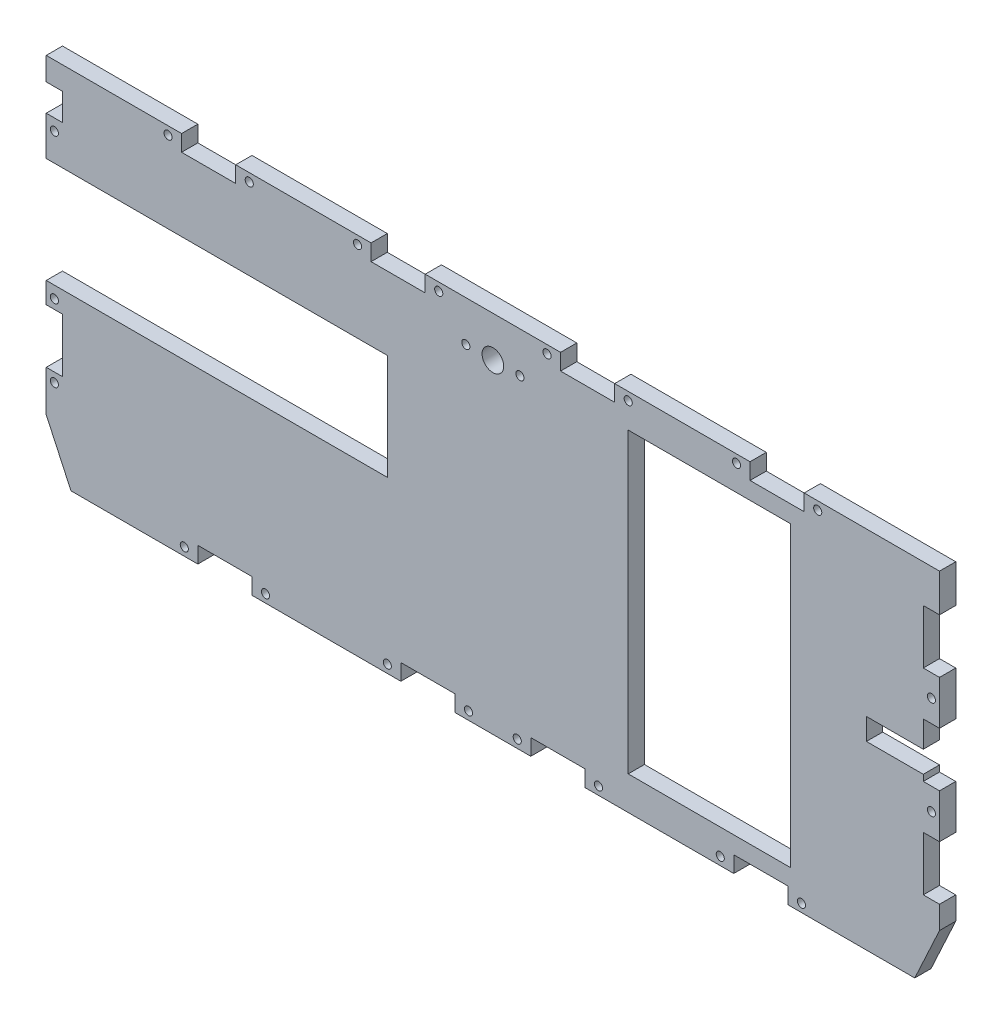
SolidWorks part; units mm, degrees
ref_plane "Plan de face" through (0, 0, 0) normal (0, 0, 1) x (1, 0, 0)
ref_plane "Plan de dessus" through (0, 0, 0) normal (0, 1, 0) x (1, 0, 0)
ref_plane "Plan de droite" through (0, 0, 0) normal (1, 0, 0) x (0, 0, -1)
sketch "Esquisse1" plane through (0, 0, 0) normal (0, 0, 1) x (1, 0, 0)
  line L0 (0, 124.9429) -> (0, -204.46) construction
  line L1 (-165, 96.73) -> (165, 96.73)
  line L2 (165, 96.73) -> (165, -18.27)
  line L3 (165, -18.27) -> (123, -109.0224)
  line L4 (123, -109.0224) -> (-123, -109.0224)
  line L5 (-211.9802, 0) -> (248.5953, 0) construction
  line L6 (-123, -109.0224) -> (-165, -18.27)
  line L7 (-165, -18.27) -> (-165, 96.73)
  dimension "D2" = 165
  dimension "D3" = 330
  dimension "D4" = 100
  dimension "D5" = 115
  dimension "D6" = 100
  dimension "D7" = 246
  dimension "D8" = 205.7524
  dimension "D9" = 96.73
  dimension "D10" = 115
extrude "Boss.-Extru.1" add sketch "Esquisse1" along normal blind 6
sketch "Esquisse3" plane through (0, 0, 0) normal (0, 0, -1) x (-1, 0, 0)
  line L0 (165, 96.73) -> (165, -18.27) construction
  line L1 (165, -3.06) -> (159, -3.06)
  line L2 (165, -3.06) -> (165, 16.94)
  line L3 (165, 16.94) -> (159, 16.94)
  line L4 (159, -3.06) -> (159, 16.94)
  line L5 (123, -109.0224) -> (-123, -109.0224) construction
  line L6 (165, 78.2326) -> (159, 78.2326)
  line L7 (165, 78.2326) -> (165, 88.2326)
  line L8 (165, 88.2326) -> (159, 88.2326)
  line L9 (159, 78.2326) -> (159, 88.2326)
  line L10 (-14, -38.02) -> (-14, -32.02)
  line L11 (109, -38.02) -> (89, -38.02)
  line L12 (109, -38.02) -> (109, -32.02)
  line L13 (109, -32.02) -> (89, -32.02)
  line L15 (0, -209.4812) -> (0, 177.1799) construction
  line L16 (-110, 84.355) -> (-50, 84.355)
  line L17 (-165, 82.73) -> (-159, 82.73)
  line L18 (89, -38.02) -> (89, -32.02)
  line L19 (34, -38.02) -> (14, -38.02)
  line L20 (34, -38.02) -> (34, -32.02)
  line L21 (34, -32.02) -> (14, -32.02)
  line L22 (-165, 82.73) -> (-165, 62.73)
  line L23 (-165, 62.73) -> (-159, 62.73)
  line L24 (-159, 82.73) -> (-159, 62.73)
  line L25 (-165, 46.44) -> (-159, 46.44)
  line L26 (-165, 46.44) -> (-165, 26.44)
  line L27 (-165, 26.44) -> (-159, 26.44)
  line L28 (-159, 46.44) -> (-159, 26.44)
  line L29 (-165, 10.15) -> (-159, 10.15)
  line L30 (-165, 96.73) -> (165, 96.73) construction
  line L31 (115, 96.73) -> (95, 96.73)
  line L32 (115, 96.73) -> (115, 90.73)
  line L33 (115, 90.73) -> (95, 90.73)
  line L34 (95, 96.73) -> (95, 90.73)
  line L35 (-25, 96.73) -> (-25, 90.73)
  line L36 (45, 96.73) -> (25, 96.73)
  line L37 (45, 96.73) -> (45, 90.73)
  line L38 (45, 90.73) -> (25, 90.73)
  line L39 (25, 96.73) -> (25, 90.73)
  line L40 (-45, 90.73) -> (-25, 90.73)
  line L41 (-45, 96.73) -> (-45, 90.73)
  line L42 (-45, 96.73) -> (-25, 96.73)
  line L43 (-95, 96.73) -> (-95, 90.73)
  line L44 (-115, 90.73) -> (-95, 90.73)
  line L45 (-115, 96.73) -> (-115, 90.73)
  line L46 (-115, 96.73) -> (-95, 96.73)
  line L47 (-165, 10.15) -> (-165, -9.85)
  line L48 (14, -38.02) -> (14, -32.02)
  line L49 (-34, -32.02) -> (-14, -32.02)
  line L50 (-34, -38.02) -> (-34, -32.02)
  line L51 (-34, -38.02) -> (-14, -38.02)
  line L52 (-165, -9.85) -> (-159, -9.85)
  line L53 (165, 63.73) -> (39, 63.73)
  line L54 (165, 63.73) -> (165, 24.73)
  line L55 (165, 24.73) -> (39, 24.73)
  line L56 (-159, 10.15) -> (-159, -9.85)
  line L57 (-89, -38.02) -> (-89, -32.02)
  line L58 (-109, -32.02) -> (-89, -32.02)
  line L59 (-109, -38.02) -> (-109, -32.02)
  line L60 (-109, -38.02) -> (-89, -38.02)
  line L62 (-110, 84.355) -> (-110, -25.645)
  line L63 (-110, -25.645) -> (-50, -25.645)
  line L64 (-50, 84.355) -> (-50, -25.645)
  line L65 (-165, -18.27) -> (-165, 96.73) construction
  line L66 (39, 63.73) -> (39, 24.73)
  dimension "D1" = 20
  dimension "D2" = 6
  dimension "D3" = 6
  dimension "D4" = 10
  dimension "D5" = 6
  dimension "D6" = 20
  dimension "D7" = 60
  dimension "D8" = 55
  dimension "D9" = 8.4974
  dimension "D10" = 20
  dimension "D11" = 20
  dimension "D12" = 50
  dimension "D13" = 50
  dimension "D14" = 6
  dimension "D15" = 110
  dimension "D16" = 56
  dimension "D17" = 55
  dimension "D18" = 20
  dimension "D19" = 20
  dimension "D20" = 20
  dimension "D21" = 6
  dimension "D22" = 6
  dimension "D23" = 20
  dimension "D24" = 71.0024
  dimension "D25" = 71.0024
  dimension "D26" = 33
  dimension "D27" = 39
  dimension "D28" = 126
  dimension "D29" = 6.375
  dimension "D30" = 15.21
  dimension "D31" = 6
  dimension "D32" = 6
  dimension "D33" = 6
  dimension "D34" = 14
  dimension "D35" = 16.29
  dimension "D36" = 16.29
extrude "Enlèv. mat.-Extru.2" cut sketch "Esquisse3" against normal blind 6
sketch "Esquisse4" plane through (0, 0, 0) normal (0, 0, -1) x (-1, 0, 0)
  line L0 (159, 78.2326) -> (165, 78.2326) construction
  line L1 (115, 90.73) -> (115, 96.73) construction
  line L2 (120.102, -35.02) -> (4.7601, -35.02) construction
  line L3 (14, -32.02) -> (14, -38.02) construction
  line L4 (34, -38.02) -> (34, -32.02) construction
  line L5 (89, -32.02) -> (89, -38.02) construction
  line L6 (26.5287, 81.73) -> (-31.7243, 81.73) construction
  line L7 (109, -38.02) -> (109, -32.02) construction
  line L8 (165, 78.2326) -> (165, 63.73) construction
  line L9 (-120.102, -35.02) -> (-4.7601, -35.02) construction
  line L10 (-25, 96.73) -> (25, 96.73) construction
  line L11 (143.8632, 93.73) -> (-5, 93.73) construction
  line L12 (45, 96.73) -> (95, 96.73) construction
  line L13 (-162, -27.3544) -> (-162, 100.425) construction
  line L14 (95, 96.73) -> (95, 90.73) construction
  line L15 (45, 90.73) -> (45, 96.73) construction
  line L16 (25, 96.73) -> (25, 90.73) construction
  line L17 (0, 142.2997) -> (0, -202.2086) construction
  line L18 (-165, -18.27) -> (-165, -9.85) construction
  line L19 (-80, 84.355) -> (-80, -25.645) construction
  line L21 (165, 16.94) -> (159, 16.94) construction
  line L22 (162, -8.8216) -> (162, 103.5789) construction
  line L25 (-50, 84.355) -> (-110, 84.355) construction
  line L26 (-110, -25.645) -> (-50, -25.645) construction
  line L27 (-159, 46.44) -> (-165, 46.44) construction
  line L28 (-165, 26.44) -> (-159, 26.44) construction
  line L31 (159, -3.06) -> (165, -3.06) construction
  circle A0 centre (162, 20.335) radius 1.5
  circle A1 centre (114, -35.02) radius 1.5
  circle A2 centre (162, 73.9826) radius 1.5
  circle A3 centre (84, -35.02) radius 1.5
  circle A4 centre (39, -35.02) radius 1.5
  circle A5 centre (162, -6.46) radius 1.5
  circle A6 centre (9, -35.02) radius 1.5
  circle A7 centre (-9, -35.02) radius 1.5
  circle A8 centre (-39, -35.02) radius 1.5
  circle A9 centre (-84, -35.02) radius 1.5
  circle A10 centre (120, 93.73) radius 1.5
  circle A11 centre (-114, -35.02) radius 1.5
  circle A12 centre (90, 93.73) radius 1.5
  circle A13 centre (0, 81.73) radius 4
  circle A14 centre (50, 93.73) radius 1.5
  circle A15 centre (20, 93.73) radius 1.5
  circle A16 centre (-162, 18.29) radius 1.5
  circle A17 centre (-162, 54.585) radius 1.5
  circle A18 centre (-20, 93.73) radius 1.5
  circle A19 centre (-50, 93.73) radius 1.5
  circle A20 centre (-90, 93.73) radius 1.5
  circle A21 centre (-120, 93.73) radius 1.5
  circle A22 centre (-10, 81.73) radius 1.5
  circle A23 centre (10, 81.73) radius 1.5
  dimension "D3" = 3
  dimension "D10" = 3
  dimension "D11" = 3
  dimension "D12" = 3
  dimension "D13" = 5
  dimension "D14" = 5
  dimension "D18" = 3
  dimension "D19" = 3
  dimension "D29" = 3
  dimension "D30" = 8.15
  dimension "D31" = 3
  dimension "D32" = 10
  dimension "D33" = 3
  dimension "D34" = 3
  dimension "D35" = 10
  dimension "D40" = 5
  dimension "D5" = 3.395
  dimension "D8" = 5
  dimension "D15" = 5
  dimension "D16" = 5
  dimension "D20" = 3.4
  dimension "D17" = 3
  dimension "D21" = 3
  dimension "D22" = 3
  dimension "D23" = 3
  dimension "D25" = 8
  dimension "D27" = 8.145
  dimension "D9" = 3
  dimension "D7" = 3
  dimension "D24" = 3
  dimension "D6" = 4.25
  dimension "D26" = 3
  dimension "D28" = 3
  dimension "D36" = 15
  dimension "D38" = 5
  dimension "D42" = 5
extrude "Enlèv. mat.-Extru.3" cut sketch "Esquisse4" against normal blind 6
sketch "Esquisse5" plane through (0, 0, 0) normal (0, 0, -1) x (-1, 0, 0)
  line L0 (45, 96.73) -> (95, 96.73) construction
  line L1 (209.7155, -38.02) -> (-246.3297, -38.02)
  line L2 (209.7155, -38.02) -> (209.7155, -174.249)
  line L3 (209.7155, -174.249) -> (-246.3297, -174.249)
  line L4 (-246.3297, -38.02) -> (-246.3297, -174.249)
  dimension "D1" = 134.75
extrude "Enlèv. mat.-Extru.4" cut sketch "Esquisse5" against normal blind 6
sketch "Esquisse6" plane through (0, 0, 0) normal (0, 0, -1) x (-1, 0, 0)
  line L0 (-159, 26.44) -> (-159, 46.44) construction
  line L1 (-159, 36.73) -> (-138, 36.73)
  line L2 (-159, 36.73) -> (-159, 28.73)
  line L3 (-159, 28.73) -> (-138, 28.73)
  line L4 (-138, 36.73) -> (-138, 28.73)
  line L5 (-165, 96.73) -> (-115, 96.73) construction
  dimension "D1" = 60
  dimension "D2" = 8
  dimension "D3" = 21
extrude "Enlèv. mat.-Extru.5" cut sketch "Esquisse6" against normal blind 10
